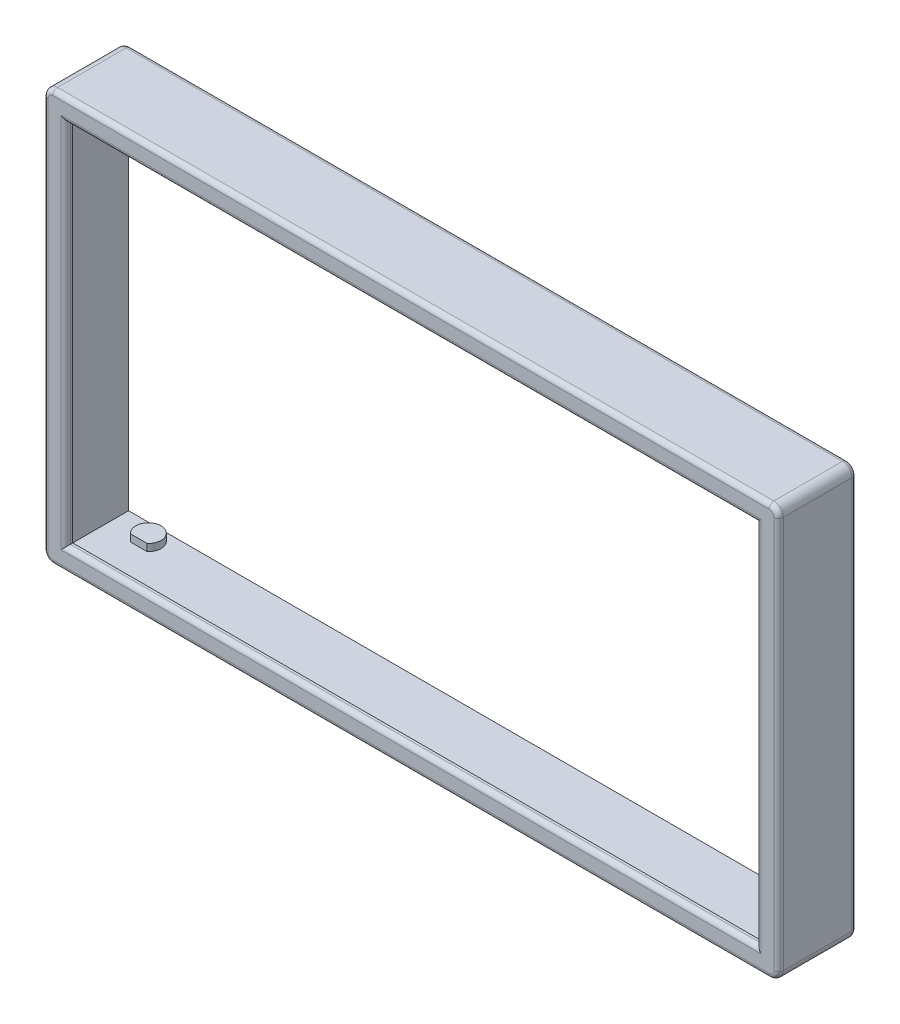
SolidWorks part; units mm, degrees
ref_plane "Front Plane" through (0, 0, 0) normal (0, 0, 1) x (1, 0, 0)
ref_plane "Top Plane" through (0, 0, 0) normal (0, 1, 0) x (1, 0, 0)
ref_plane "Right Plane" through (0, 0, 0) normal (1, 0, 0) x (0, 0, -1)
sketch "Sketch1" plane through (0, 0, 120.1349) normal (0, 0, 1) x (1, 0, 0)
  line L4 (49.279, -67.677) -> (49.279, 15.903)
  line L5 (49.279, 15.903) -> (-102.721, 15.903)
  line L6 (-102.721, 15.903) -> (-102.721, -67.677)
  line L7 (-102.721, -67.677) -> (49.279, -67.677)
  line L8 (49.279, -67.677) -> (49.279, 15.903) construction
  line L9 (49.279, 15.903) -> (-102.721, 15.903) construction
  line L10 (-102.721, 15.903) -> (-102.721, -67.677) construction
  line L11 (-102.721, -67.677) -> (49.279, -67.677) construction
  line L12 (-104.421, 17.603) -> (-104.421, -69.377)
  line L13 (-104.421, -69.377) -> (50.979, -69.377)
  line L14 (50.979, -69.377) -> (50.979, 17.603)
  line L15 (50.979, 17.603) -> (-104.421, 17.603)
  line L16 (49.479, -67.877) -> (49.479, 16.103)
  line L17 (49.479, 16.103) -> (-102.921, 16.103)
  line L18 (-102.921, 16.103) -> (-102.921, -67.877)
  line L19 (-102.921, -67.877) -> (49.479, -67.877)
  line L20 (49.479, -67.877) -> (49.479, 16.103)
  line L21 (49.479, 16.103) -> (-102.921, 16.103)
  line L22 (-102.921, 16.103) -> (-102.921, -67.877)
  line L23 (-102.921, -67.877) -> (49.479, -67.877)
  line L24 (46.279, -64.677) -> (46.279, 12.903)
  line L25 (46.279, 12.903) -> (-99.721, 12.903)
  line L26 (-99.721, 12.903) -> (-99.721, -64.677)
  line L27 (-99.721, -64.677) -> (46.279, -64.677)
  dimension "D1" = 0
  dimension "D2" = 0.2
  dimension "D3" = 1.5
  dimension "D4" = 3
extrude "Boss-Extrude1" add sketch "Sketch1" along normal blind 1.5 contours L14 L15 L12 L13 L23 L22 L21 L20 | L22 L23 L20 L21 L27 L26 L25 L24 region at (-26.721, -65.9423, 120.1349) region at (-26.721, 17.4249, 120.1349) region at (-26.721, -67.703, 120.1349)
extrude "Boss-Extrude2" add sketch "Sketch1<3>" against normal blind 15 contours L14 L15 L12 L13 L23 L22 L21 L20 region at (-26.721, 17.4249, 120.1349)
sketch "Sketch1<3>" plane through (0, 0, 120.1349) normal (0, 0, 1) x (1, 0, 0) same geometry as "Sketch1"
fillet "Fillet1" radius 2 4 edges at (-104.421, -69.377, 113.3849) (-104.421, 17.603, 113.3849) (50.979, 17.603, 113.3849) (50.979, -69.377, 113.3849)
fillet "Fillet2" radius 1 20 edges at (50.3932, -68.7912, 105.1349) (-26.721, -69.377, 105.1349) (-103.8353, -68.7912, 105.1349) (-104.421, -25.887, 105.1349) (-103.8353, 17.0172, 105.1349) (-26.721, 17.603, 105.1349) (50.3932, 17.0172, 105.1349) (46.279, -25.887, 121.6349) (-26.721, 12.903, 121.6349) (-99.721, -25.887, 121.6349) (-26.721, -64.677, 121.6349) (-103.8353, 17.0172, 121.6349) (-26.721, 17.603, 121.6349) (50.3932, 17.0172, 121.6349) (50.979, -25.887, 121.6349) (50.3932, -68.7912, 121.6349) (-26.721, -69.377, 121.6349) (-103.8353, -68.7912, 121.6349) (-104.421, -25.887, 121.6349) (50.979, -25.887, 105.1349)
sketch "Sketch2" plane through (0, -67.877, 0) normal (0, 1, 0) x (1, 0, 0)
  line L0 (43.529, -110.6581) -> (40.029, -110.6581)
  line L1 (-93.471, -110.6581) -> (-96.971, -110.6581)
  circle A0 centre (41.779, -108.6349) radius 2.875 construction
  circle A1 centre (-95.221, -108.6349) radius 2.875 construction
  circle A2 centre (41.779, -108.6349) radius 2.875 construction
  circle A3 centre (-95.221, -108.6349) radius 2.875 construction
  circle A4 centre (41.779, -108.6349) radius 2.675
  circle A5 centre (-95.221, -108.6349) radius 2.675
  dimension "D2" = 3.5
  dimension "D4" = 3.5
  dimension "D1" = 0.2
  dimension "D3" = 0.2
extrude "Boss-Extrude3" add sketch "Sketch2" along normal blind 1.5 contours L1 A5 | L0 A4 region at (41.779, -67.877, 108.4641) region at (-95.221, -67.877, 108.4641)
extrude "Boss-Extrude4" add sketch "Sketch2<3>" against normal blind 0.85 from surface contours L1 A5 | A4 region at (-95.221, -67.877, 108.4641) starting at face at (-26.721, 16.103, 112.6349)
sketch "Sketch2<3>" plane through (0, -67.877, 0) normal (0, 1, 0) x (1, 0, 0) same geometry as "Sketch2"
